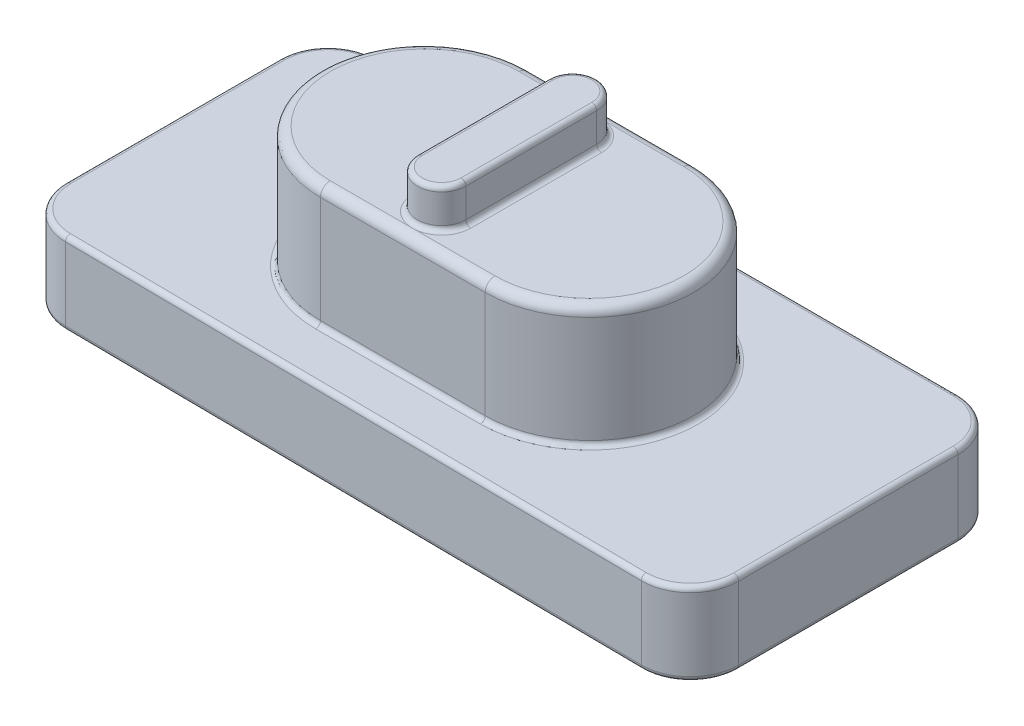
SolidWorks part; units mm, degrees
ref_plane "前视基准面" through (0, 0, 0) normal (0, 0, 1) x (1, 0, 0)
ref_plane "上视基准面" through (0, 0, 0) normal (0, 1, 0) x (1, 0, 0)
ref_plane "右视基准面" through (0, 0, 0) normal (1, 0, 0) x (0, 0, -1)
sketch "草图1" plane through (0, 0, 0) normal (0, 1, 0) x (1, 0, 0)
  line L0 (-1.7, 0) -> (1.7, 0) construction
  line L1 (-1.7, 2.15) -> (1.7, 2.15)
  line L2 (-1.7, -2.15) -> (1.7, -2.15)
  arc A0 (-1.7, 2.15) -> (-1.7, -2.15) centre (-1.7, 0) ccw
  arc A1 (1.7, -2.15) -> (1.7, 2.15) centre (1.7, 0) ccw
  point P2 (0, 0)
  point P8 (-3.85, 0)
  point P9 (3.85, 0)
  dimension "D1" = 7.7
  dimension "D2" = 4.3
extrude "凸台-拉伸1" add sketch "草图1" along normal blind 2.5
fillet "圆角1" radius 0.2 4 edges at (0, 2.5, -2.15) (3.85, 2.5, 0) (0, 2.5, 2.15) (-3.85, 2.5, 0)
sketch "草图2" plane through (0, 2.5, 0) normal (0, 1, 0) x (1, 0, 0)
  line L0 (0, 1.35) -> (0, -1.35) construction
  line L1 (0.5, 1.35) -> (0.5, -1.35)
  line L2 (-0.5, 1.35) -> (-0.5, -1.35)
  line L3 (1.7, -2.15) -> (-1.7, -2.15) construction
  arc A0 (0.5, 1.35) -> (-0.5, 1.35) centre (0, 1.35) ccw
  arc A1 (-0.5, -1.35) -> (0.5, -1.35) centre (0, -1.35) ccw
  point P2 (0, 0)
  point P8 (0, -1.85)
  dimension "D1" = 1
  dimension "D2" = 0.3
extrude "凸台-拉伸2" add sketch "草图2" along normal blind 0.8
fillet "圆角2" radius 0.1 4 edges at (0.5, 3.3, 0) (0, 3.3, 1.85) (-0.5, 3.3, 0) (0, 3.3, -1.85)
sketch "草图3" plane through (0, 0, 0) normal (0, -1, 0) x (1, 0, 0)
  line L2 (-6.9264, 3.1663) -> (-6.9264, -3.2337)
  line L3 (-6.9264, -3.2337) -> (7.0736, -3.2337)
  line L4 (7.0736, 3.3024) -> (7.0736, -3.2337)
  line L5 (-6.9264, 3.1663) -> (7.0736, -3.2337) construction
  line L6 (-6.9264, -3.2337) -> (7.0736, 3.3024) construction
  line L9 (-6.9264, 3.1663) -> (7.0736, 3.3024)
  point P0 (0, 0)
  dimension "D1" = 6.4
  dimension "D2" = 14
extrude "凸台-拉伸3" add sketch "草图3" along normal blind 1.7
fillet "圆角3" radius 0.1 12 edges at (-6.9264, 0, -0.0337) (0.0736, 0, -3.2337) (7.0736, 0, 0.0344) (0, 0, 2.15) (3.85, 0, 0) (0, 0, -2.15) (-3.85, 0, 0) (0.0736, -1.7, -3.2337) (-6.9264, -1.7, -0.0337) (7.0736, -1.7, 0.0344) (0.0736, 0, 3.2344) (0.0736, -1.7, 3.2344)
fillet "圆角4" radius 1 12 edges at (-6.8971, -0.0293, -3.2044) (-6.8971, -1.6707, -3.2044) (7.0444, -0.0293, -3.2044) (7.0444, -1.6707, -3.2044) (7.0736, -0.85, -3.2337) (-6.9264, -0.85, -3.2337) (7.0444, -0.0293, 3.2729) (7.0444, -1.6707, 3.2729) (-6.8971, -0.0293, 3.1373) (-6.8971, -1.6707, 3.1373) (-6.9264, -0.85, 3.1663) (7.0736, -0.85, 3.3024)
sketch "草图5" plane through (0, -1.7, 0) normal (0, -1, 0) x (1, 0, 0)
  line L1 (-1.025, 1.8) -> (1.025, 1.8)
  line L2 (-1.025, 1.8) -> (-1.025, -1.8)
  line L3 (-1.025, -1.8) -> (1.025, -1.8)
  line L4 (1.025, 1.8) -> (1.025, -1.8)
  line L5 (-1.025, 1.8) -> (1.025, -1.8) construction
  line L6 (-1.025, -1.8) -> (1.025, 1.8) construction
  point P0 (0, 0)
  dimension "D1" = 2.05
  dimension "D2" = 3.6
extrude "切除-拉伸1" cut sketch "草图5" against normal offset from surface (3.2 mm away) 1 up to face at (0, 2.5, 0)
fillet "圆角5" radius 0.1 4 edges at (1.025, -1.7, 0) (0, -1.7, 1.8) (-1.025, -1.7, 0) (0, -1.7, -1.8)
fillet "圆角6" radius 0.1 4 edges at (0, 2.5, 1.85) (-0.5, 2.5, 0) (0, 2.5, -1.85) (0.5, 2.5, 0)
